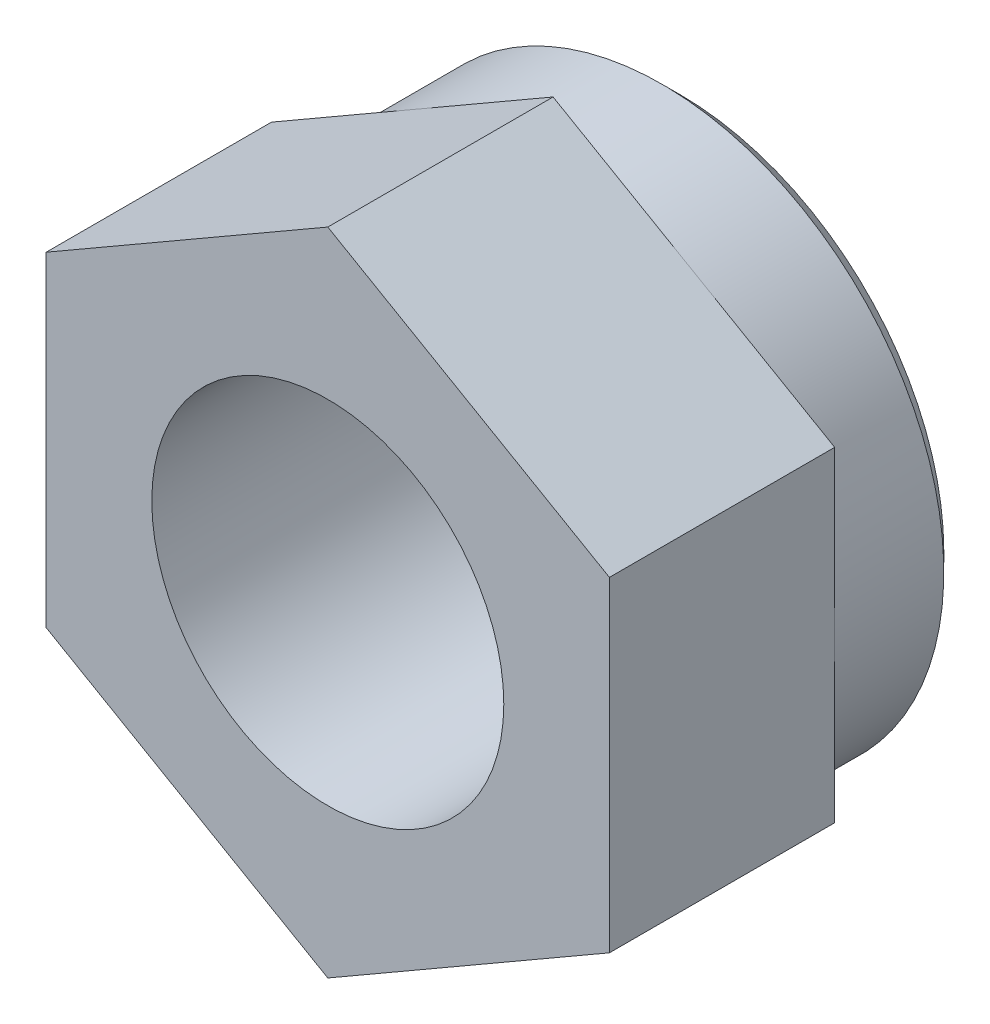
SolidWorks part; units mm, degrees
material "镀铬不锈钢"
ref_plane "前视基准面" through (0, 0, 0) normal (0, 0, 1) x (1, 0, 0)
ref_plane "上视基准面" through (0, 0, 0) normal (0, 1, 0) x (1, 0, 0)
ref_plane "右视基准面" through (0, 0, 0) normal (1, 0, 0) x (0, 0, -1)
sketch "Sketch1" plane through (0, 0, 0) normal (0, 0, 1) x (1, 0, 0)
  line L1 (0, 4.6188) -> (-4, 2.3094)
  line L2 (-4, 2.3094) -> (-4, -2.3094)
  line L3 (-4, -2.3094) -> (0, -4.6188)
  line L4 (0, -4.6188) -> (4, -2.3094)
  line L5 (4, -2.3094) -> (4, 2.3094)
  line L6 (4, 2.3094) -> (0, 4.6188)
  circle A0 centre (0, 0) radius 4 construction
  circle A1 centre (0, 0) radius 2.5
  dimension "D2" = 5
  dimension "D1" = 8
extrude "Extrude1" add sketch "Sketch1" along normal blind 3.2
sketch "Sketch2" plane through (0, 0, 0) normal (0, 0, -1) x (-1, 0, 0)
  line L0 (-4, -2.3094) -> (-4, 2.3094) construction
  circle A0 centre (0, 0) radius 2.5 construction
  circle A1 centre (0, 0) radius 2.5
  circle A2 centre (0, 0) radius 4
extrude "Extrude2" add sketch "Sketch2" along normal blind 1.8
chamfer "Chamfer1" distance 0.25 angle 45 2 edges at (-2.5, 0, -1.8) (-4, 0, -1.8)
